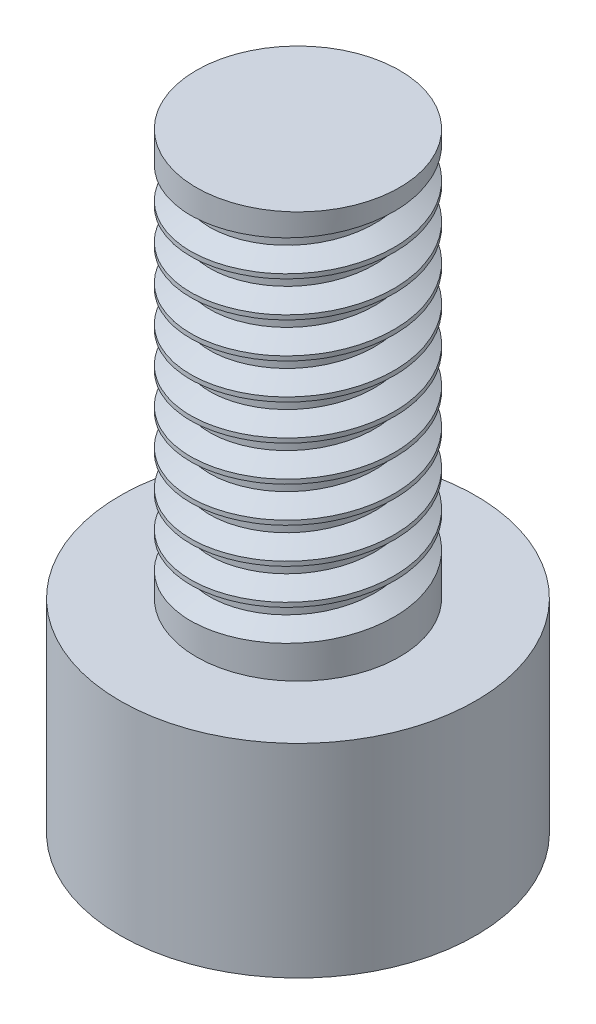
SolidWorks part; units mm, degrees
ref_plane "Front Plane" through (0, 0, 0) normal (0, 0, 1) x (1, 0, 0)
ref_plane "Top Plane" through (0, 0, 0) normal (0, 1, 0) x (1, 0, 0)
ref_plane "Right Plane" through (0, 0, 0) normal (1, 0, 0) x (0, 0, -1)
sketch "Sketch1" plane through (0, 0, 0) normal (0, 1, 0) x (1, 0, 0)
  circle A0 centre (0, 0) radius 3.5
  dimension "D1" = 7
extrude "Boss-Extrude1" add sketch "Sketch1" along normal blind 4
sketch "Sketch2" plane through (0, 4, 0) normal (0, 1, 0) x (1, 0, 0)
  circle A0 centre (0, 0) radius 2
extrude "Boss-Extrude2" add sketch "Sketch2" along normal blind 8
sketch "Sketch3" plane through (0, 0, 0) normal (0, -1, 0) x (1, 0, 0)
  line L1 (1.1678, -1.9924) -> (2.3094, 0.0152)
  line L2 (2.3094, 0.0152) -> (1.1415, 2.0076)
  line L3 (1.1415, 2.0076) -> (-1.1678, 1.9924)
  line L4 (-1.1678, 1.9924) -> (-2.3094, -0.0152)
  line L5 (-2.3094, -0.0152) -> (-1.1415, -2.0076)
  line L6 (-1.1415, -2.0076) -> (1.1678, -1.9924)
  circle A0 centre (0, 0) radius 2 construction
  dimension "D1" = 4
extrude "Cut-Extrude1" cut sketch "Sketch3" against normal blind 2.5
thread "Thread1" pitch 0.7 method cut profile "Thread Profile1" start angle 0, offset 0, length 7, pitch 0.7, diameter 4
ref_plane "Plane1" through (-2, 12, 0) normal (0, 0, 1) x (-1, 0, 0)
sketch "Thread Profile1" plane through (-2, 12, 0) normal (0, 0, 1) x (-1, 0, 0)
  line L0 (0, 0) -> (0, 0.7) construction
  line L11 (0, 0) -> (0, 0.6125)
  line L12 (0, 0.6125) -> (-0.3789, 0.3937)
  line L13 (-0.3789, 0.3937) -> (-0.3789, 0.2187)
  line L15 (-0.3789, 0.2187) -> (0, 0)
  line L17 (-0.3789, 0.3062) -> (0, 0.3062) construction
  point P2 (0, 0)
  dimension "Pitch" = 0.7
  dimension "Profile_Angle" = 60
  dimension "Profile_Land" = 0.175
  dimension "Profile_Height" = 0.3789
